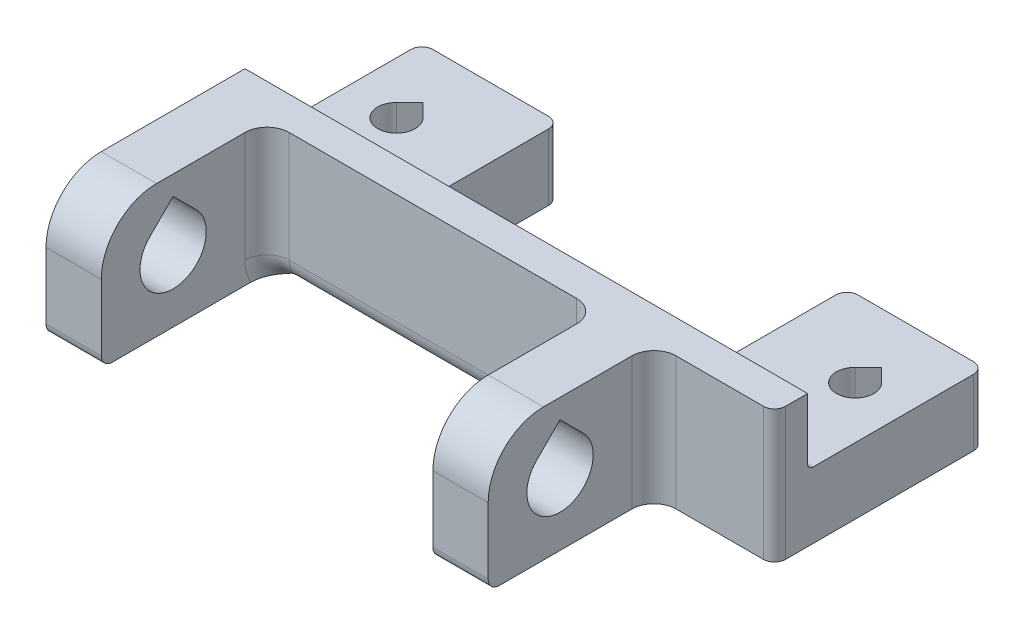
SolidWorks part; units mm, degrees
ref_plane "Front" through (0, 0, 0) normal (0, 0, 1) x (1, 0, 0)
ref_plane "Top" through (0, 0, 0) normal (0, 1, 0) x (1, 0, 0)
ref_plane "Right" through (0, 0, 0) normal (1, 0, 0) x (0, 0, -1)
other "Configuration Table"
sketch "Sketch1" plane through (0, 0, 0) normal (0, 1, 0) x (1, 0, 0)
  line L0 (0, -12.9075) -> (0, 28.1756) construction
  line L1 (-13, 5) -> (13, 5)
  line L2 (13, 5) -> (13, 16)
  line L3 (13, 16) -> (25.45, 16)
  line L5 (25.45, 0) -> (-25.45, 0)
  line L7 (-13, 16) -> (-25.45, 16)
  line L8 (-13, 5) -> (-13, 16)
  line L9 (-20.75, 29.8589) -> (-20.75, -7.0506) construction
  line L10 (-21.9521, 10.2021) -> (-20.75, 11.4042)
  line L11 (-19.5479, 10.2021) -> (-20.75, 11.4042)
  line L12 (21.9521, 10.2021) -> (20.75, 11.4042)
  line L13 (19.5479, 10.2021) -> (20.75, 11.4042)
  line L14 (-25.45, 16) -> (-25.45, -18)
  line L15 (-25.45, -18) -> (-20.45, -18)
  line L16 (-20.45, -18) -> (-20.45, -3)
  line L26 (25.45, 16) -> (25.45, 0)
  line L27 (-20.45, -3) -> (9.55, -3)
  line L28 (9.55, -3) -> (9.55, -18)
  line L29 (9.55, -18) -> (14.55, -18)
  line L30 (14.55, -18) -> (14.55, -3)
  line L31 (14.55, -3) -> (25.45, -3)
  line L32 (25.45, -3) -> (25.45, 0)
  arc A0 (-21.9521, 10.2021) -> (-19.5479, 10.2021) centre (-20.75, 9) ccw
  arc A2 (21.9521, 10.2021) -> (19.5479, 10.2021) centre (20.75, 9) cw
  point P30 (13.95, -3)
  dimension "D5" = 3.4
  dimension "D1" = 26
  dimension "D2" = 11
  dimension "D3" = 7
  dimension "26" = 16
  dimension "D4" = 41.5
  dimension "D6" = 3
  dimension "D7" = 18
  dimension "D8" = 3
  dimension "D9" = 30
  dimension "D10" = 5
extrude "Boss-Extrude2" add sketch "Sketch1" along normal blind 6 contours L1 L8 L7 L5 L3 L2 A0 L10 L11 L12 A2 L13 region at (0, 0, -4.4664)
extrude "Boss-Extrude4" add sketch "Sketch1<4>" along normal offset from surface (12 mm away) 6 contours L5 L14 L15 L16 region at (0, 0, 0.5399) up to face at (-20.75, 6, -9.6354) offset beyond the face yes
sketch "Sketch1<4>" plane through (0, 0, 0) normal (0, 1, 0) x (1, 0, 0) same geometry as "Sketch1"
sketch "Sketch9" plane through (-25.45, 0, 0) normal (-1, 0, 0) x (0, 0, 1)
  line L0 (11.5, 14.3717) -> (11.5, -5.6761) construction
  line L4 (9.3787, 8.1213) -> (11.5, 10.2426)
  line L5 (11.5, 10.2426) -> (13.6213, 8.1213)
  line L8 (18, 12) -> (18, 0) construction
  line L10 (0, 12) -> (18, 12) construction
  arc A0 (9.3787, 8.1213) -> (13.6213, 8.1213) centre (11.5, 6) ccw
  dimension "D1" = 6
  dimension "D4" = 6
  dimension "D3" = 6.5
extrude "Cut-Extrude4" cut sketch "Sketch9" against normal through all
fillet "Fillet3" radius 5 2 edges at (-22.95, 12, 18) (12.05, 12, 18)
fillet "Fillet7" radius 2 1 edges at (-5.45, 0, 3)
fillet "Fillet4" radius 2 5 edges at (9.55, 7, 3) (14.55, 6, 3) (-20.45, 7, 3) (9.55, 0.5858, 2.4142) (-20.45, 0.5858, 2.4142)
fillet "Fillet5" radius 0.5 1 edges at (0, 6, 0)
fillet "Fillet6" radius 1 7 edges at (-13, 3, -16) (25.45, 3, -16) (13, 3, -16) (-22.95, 0, 18) (-25.45, 3, -16) (25.45, 6, 3) (12.05, 0, 18)
